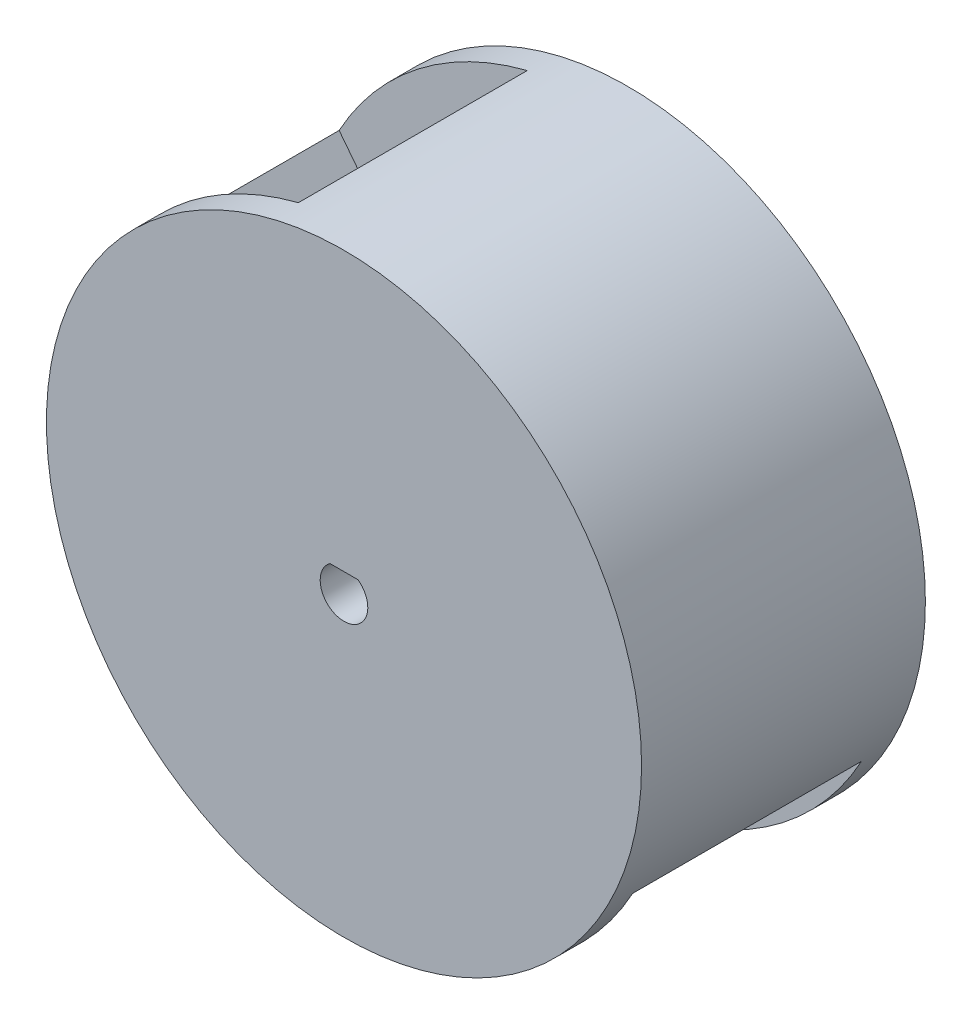
SolidWorks part; units mm, degrees
ref_plane "Front Plane" through (0, 0, 0) normal (0, 0, 1) x (1, 0, 0)
ref_plane "Top Plane" through (0, 0, 0) normal (0, 1, 0) x (1, 0, 0)
ref_plane "Right Plane" through (0, 0, 0) normal (1, 0, 0) x (0, 0, -1)
sketch "Sketch2" plane through (0, 0, 0) normal (0, 0, 1) x (1, 0, 0)
  circle A0 centre (0, 0) radius 32.5
  dimension "D2" = 65
extrude "Boss-Extrude1" add sketch "Sketch2" along normal blind 3
sketch "Sketch3" plane through (0, 0, 3) normal (0, 0, 1) x (1, 0, 0)
  line L0 (0, 7.5) -> (0, 21.2104)
  line L1 (0, -7.5) -> (0, -21.2104)
  line L4 (-20.544, 5.2748) -> (-7.2644, 1.8652)
  line L5 (7.2644, -1.8652) -> (20.544, -5.2748)
  line L6 (-32.5, 0) -> (32.5, 0) construction
  line L7 (-7.2644, 1.8652) -> (7.2644, -1.8652) construction
  line L8 (4.5968, -5.9262) -> (-19.9195, 25.68) construction
  line L9 (-20.544, 5.2748) -> (-28.5285, 15.5684)
  line L10 (0, 21.2104) -> (-7.9845, 31.5039)
  line L11 (0, -21.2104) -> (7.9845, -31.5039)
  line L12 (20.544, -5.2748) -> (28.5285, -15.5684)
  circle A1 centre (0, 0) radius 32.5 construction
  circle A6 centre (0, 0) radius 32.5 construction
  arc A7 (0, 7.5) -> (-7.2644, 1.8652) centre (0, 0) ccw
  arc A8 (-31.479, 8.0824) -> (0, -32.5) centre (0, 0) ccw
  arc A9 (31.479, -8.0824) -> (0, 32.5) centre (0, 0) ccw
  arc A10 (0, -7.5) -> (7.2644, -1.8652) centre (0, 0) ccw
  arc A12 (-31.479, 8.0824) -> (-28.5285, 15.5684) centre (0, 0) cw
  arc A13 (-7.9845, 31.5039) -> (0, 32.5) centre (0, 0) cw
  arc A14 (31.479, -8.0824) -> (28.5285, -15.5684) centre (0, 0) cw
  arc A15 (0, -32.5) -> (7.9845, -31.5039) centre (0, 0) ccw
  point P1 (-0.0299, 32.5)
  point P10 (0, 0)
  point P34 (0, 0)
  dimension "D1" = 15
  dimension "D3" = 14.4
  dimension "D4" = 26
  dimension "D5" = 26
extrude "Boss-Extrude2" add sketch "Sketch3" along normal blind 25
sketch "Sketch4" plane through (0, 0, 28) normal (0, 0, 1) x (1, 0, 0)
  circle A0 centre (0, 0) radius 32.5
  dimension "D1" = 65
extrude "Boss-Extrude3" add sketch "Sketch4" along normal blind 3
sketch "Sketch5" plane through (0, 0, 31) normal (0, 0, 1) x (1, 0, 0)
  line L0 (-1.533, 2.1) -> (1.533, 2.1)
  arc A0 (-1.533, 2.1) -> (1.533, 2.1) centre (0, 0) ccw
  dimension "D1" = 5.2
  dimension "D2" = 2.1
extrude "Cut-Extrude1" cut sketch "Sketch5" against normal through all
